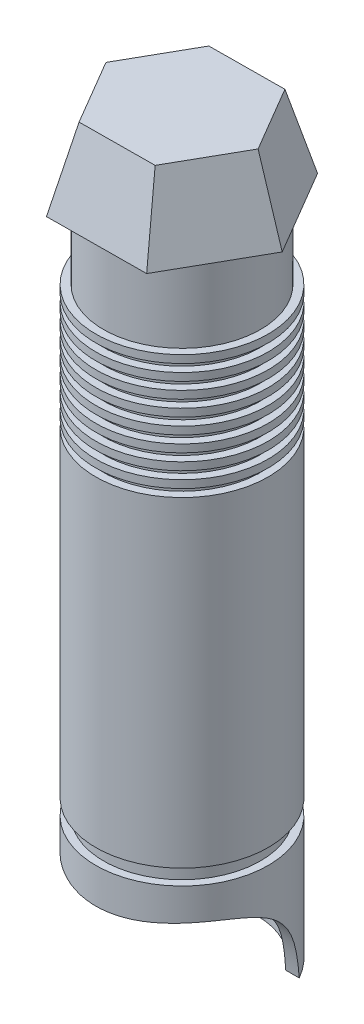
SolidWorks part; units mm, degrees
ref_plane "Front Plane" through (0, 0, 0) normal (0, 0, 1) x (1, 0, 0)
ref_plane "Top Plane" through (0, 0, 0) normal (0, 1, 0) x (1, 0, 0)
ref_plane "Right Plane" through (0, 0, 0) normal (1, 0, 0) x (0, 0, -1)
sketch "Sketch2" plane through (0, 0, 0) normal (0, 0, 1) x (1, 0, 0)
  line L0 (0, 0) -> (0, 140) construction
  line L1 (0, 140) -> (-40.8127, 140) construction
  line L2 (0, 0) -> (-38.7707, 0) construction
  line L5 (-19.3, 0) -> (-19.3, 140)
  line L7 (-20.3, 140) -> (-20.3, 121)
  line L9 (-20.3, 0) -> (-19.3, 0)
  line L11 (-19.3, 140) -> (0, 140)
  line L12 (-20.3, 140) -> (-20.3, 141)
  line L13 (-20.3, 141) -> (0, 141)
  line L14 (0, 140) -> (0, 141)
  line L15 (-20.3, 121) -> (-22.3, 121)
  line L17 (-20.3, 119) -> (-22.3, 119)
  line L18 (-22.3, 121) -> (-22.3, 119)
  line L19 (-20.3, 117) -> (-22.3, 117)
  line L20 (-22.3, 117) -> (-22.3, 115)
  line L21 (-20.3, 115) -> (-22.3, 115)
  line L23 (-20.3, 113) -> (-22.3, 113)
  line L24 (-22.3, 113) -> (-22.3, 111)
  line L25 (-20.3, 111) -> (-22.3, 111)
  line L27 (-20.3, 109) -> (-22.3, 109)
  line L28 (-22.3, 109) -> (-22.3, 107)
  line L29 (-20.3, 107) -> (-22.3, 107)
  line L31 (-20.3, 105) -> (-22.3, 105)
  line L32 (-22.3, 105) -> (-22.3, 103)
  line L33 (-20.3, 103) -> (-22.3, 103)
  line L35 (-20.3, 101) -> (-22.3, 101)
  line L36 (-22.3, 101) -> (-22.3, 99)
  line L37 (-20.3, 99) -> (-22.3, 99)
  line L39 (-20.3, 97) -> (-22.3, 97)
  line L40 (-22.3, 97) -> (-22.3, 95)
  line L41 (-20.3, 95) -> (-22.3, 95)
  line L43 (-20.3, 93) -> (-22.3, 93)
  line L44 (-22.3, 93) -> (-22.3, 91)
  line L45 (-20.3, 91) -> (-22.3, 91)
  line L46 (-20.3, 91) -> (-20.3, 89)
  line L47 (-20.3, 89) -> (-22.3, 89)
  line L49 (-20.3, 0) -> (-22.3, 0)
  line L50 (-22.3, 89) -> (-22.3, 6)
  line L51 (-22.3, 6) -> (-20.3, 6)
  line L53 (-22.3, 2) -> (-20.3, 2)
  line L54 (-20.3, 6) -> (-20.3, 2)
  line L55 (-20.3, 95) -> (-20.3, 93)
  line L56 (-22.3, 2) -> (-22.3, 0)
  line L59 (-20.3, 99) -> (-20.3, 97)
  line L61 (-20.3, 103) -> (-20.3, 101)
  line L63 (-20.3, 107) -> (-20.3, 105)
  line L65 (-20.3, 111) -> (-20.3, 109)
  line L67 (-20.3, 115) -> (-20.3, 113)
  line L69 (-20.3, 119) -> (-20.3, 117)
  dimension "D1" = 1
  dimension "D2" = 19.3
  dimension "D3" = 1
  dimension "D4" = 2
  dimension "D5" = 140
  dimension "D6" = 2
  dimension "D7" = 20
  dimension "D9" = 2
  dimension "D10" = 30
  dimension "D11" = 2
  dimension "D12" = 2
  dimension "D13" = 4
  dimension "D14" = 141
  dimension "D8" = 8
revolve "Revolve1" add sketch "Sketch2" angle 360 about L0
sketch "Sketch3" plane through (0, 141, 0) normal (0, 1, 0) x (1, 0, 0)
  line L1 (12.6856, 22.3684) -> (-13.0288, 22.1703)
  line L2 (-13.0288, 22.1703) -> (-25.7144, -0.1981)
  line L3 (-25.7144, -0.1981) -> (-12.6856, -22.3684)
  line L4 (-12.6856, -22.3684) -> (13.0288, -22.1703)
  line L5 (13.0288, -22.1703) -> (25.7144, 0.1981)
  line L6 (25.7144, 0.1981) -> (12.6856, 22.3684)
  circle A0 centre (0, 0) radius 22.27 construction
  circle A2 centre (0, 0) radius 22.3 construction
  dimension "D1" = 22.27
extrude "Boss-Extrude2" add sketch "Sketch3" along normal blind 20 draft 15 contours L1 L2 L3 L4 L5 L6
sketch "Sketch5" plane through (0, 0, 0) normal (0, -1, 0) x (1, 0, 0)
  circle A0 centre (0, 0) radius 22.3
  circle A1 centre (0, 0) radius 19.3
extrude "Boss-Extrude3" add sketch "Sketch5" along normal blind 30
sketch "Sketch6" plane through (0, 0, 0) normal (1, 0, 0) x (0, 0, -1)
  spline S0 degree 2 poles (-29.5141, -8.8446) (10.5665, 2.8283) (11.4515, -38.2975) knots 0 0 0 1 1 1
  spline S1 degree 2 poles (-29.5141, -8.8446) (-38.2659, -53.6377) (11.4515, -38.2975) knots 0 0 0 1 1 1
extrude "Cut-Extrude1" cut sketch "Sketch6" against normal blind 30 and the other way blind 30
